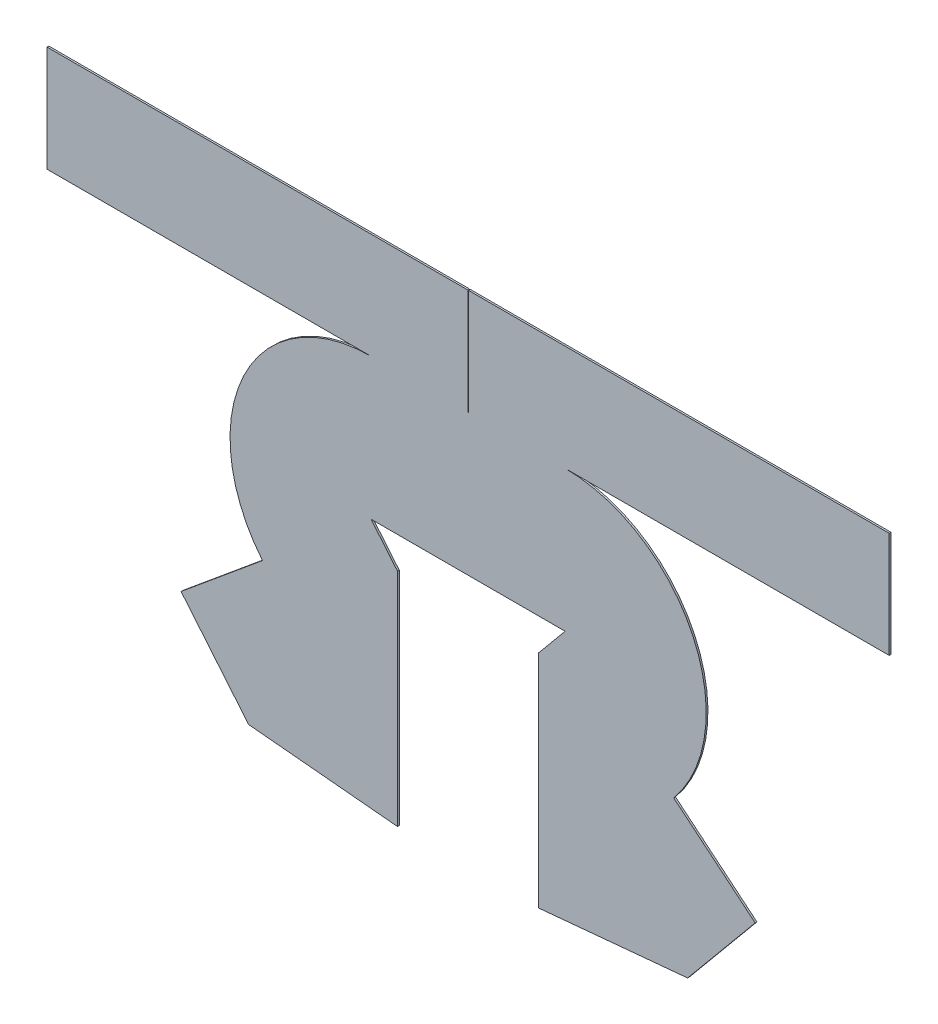
SolidWorks part; units mm, degrees
ref_plane "Front Plane" through (0, 0, 0) normal (0, 0, 1) x (1, 0, 0)
ref_plane "Top Plane" through (0, 0, 0) normal (0, 1, 0) x (1, 0, 0)
ref_plane "Right Plane" through (0, 0, 0) normal (1, 0, 0) x (0, 0, -1)
sketch "Sketch1" plane through (0, 0, 0) normal (0, 0, 1) x (1, 0, 0)
  line L0 (280.77, 169.165) -> (242.67, 123.2081)
  line L3 (1.37, 372.365) -> (280.77, 372.365)
  line L8 (1.37, 169.165) -> (39.47, 123.2081)
  line L11 (39.47, 169.165) -> (242.67, 169.165)
  line L13 (242.67, -195.1723) -> (242.67, 123.2081)
  line L17 (39.47, 123.2081) -> (39.47, -195.1723)
  line L20 (1.37, 169.165) -> (39.47, 169.165)
  line L21 (280.77, 169.165) -> (242.67, 169.165)
  line L22 (437.2026, 39.4766) -> (242.67, -195.1723)
  line L23 (1.37, 372.365) -> (280.77, 372.365)
  line L25 (-24.03, 524.765) -> (280.77, 524.765)
  line L27 (-24.03, 524.765) -> (-465.4695, 524.765)
  line L29 (1.37, 372.365) -> (-465.4695, 372.365)
  line L30 (-465.4695, 524.765) -> (-465.4695, 372.365)
  line L31 (-155.0626, 39.4766) -> (39.47, -195.1723)
  line L32 (-272.387, -57.7897) -> (-175.1207, -175.1141)
  line L33 (1.37, 372.365) -> (1.37, 169.165)
  line L34 (280.77, 372.365) -> (280.77, 169.165)
  line L36 (280.77, 372.365) -> (747.6096, 372.365)
  line L38 (280.77, 524.765) -> (747.6096, 524.765)
  line L39 (747.6096, 372.365) -> (747.6096, 524.765)
  line L42 (-175.1207, -175.1141) -> (39.47, -195.1723)
  line L43 (-272.387, -57.7897) -> (-155.0626, 39.4766)
  line L44 (554.5271, -57.7897) -> (457.2608, -175.1141)
  line L45 (457.2608, -175.1141) -> (242.67, -195.1723)
  line L46 (554.5271, -57.7897) -> (437.2026, 39.4766)
  arc A2 (1.37, 372.365) -> (-155.0626, 39.4766) centre (1.37, 169.165) ccw
  arc A3 (280.77, 372.365) -> (437.2026, 39.4766) centre (280.77, 169.165) cw
  dimension "D4" = 203.2
  dimension "D5" = 304.8
  dimension "D11" = 152.4
  dimension "D12" = 279.4
  dimension "D3" = 203.2
  dimension "D8" = 203.2
  dimension "D2" = 203.2
  dimension "D6" = 279.4
  dimension "D7" = 304.8
  dimension "D10" = 203.2
  dimension "D14" = 152.4
  dimension "D16" = 466.8396
  dimension "D19" = 152.4
extrude "Boss-Extrude2" add sketch "Sketch1" along normal blind 2.54 contours L34 L3 L33 L20 L11 L21 | L36 L39 L38 L25 L27 L30 L29 L3 | L33 A2 L31 L17 L8 | A3 L34 L0 L13 L22 | L44 L46 L22 L45 | L43 L32 L42 L31 region at (348.2201, 124.0791, 0) region at (141.07, 270.765, 0) region at (141.07, 448.565, 0) region at (413.6952, -95.0052, 0) region at (-66.0801, 124.0791, 0) region at (-131.5552, -95.0052, 0)
sketch "Sketch2" plane through (0, 0, 2.54) normal (0, 0, 1) x (1, 0, 0)
  line L0 (140.6731, 524.765) -> (140.6731, 372.365)
  line L1 (-465.4695, 524.765) -> (747.6096, 524.765) construction
  line L2 (140.6731, 372.365) -> (141.4669, 372.365)
  line L3 (141.4669, 372.365) -> (141.4669, 524.765)
  line L4 (141.4669, 524.765) -> (140.6731, 524.765)
  dimension "D1" = 0.7937
  dimension "D2" = 139.3031
extrude "Cut-Extrude1" cut sketch "Sketch2" against normal blind 55.5254
